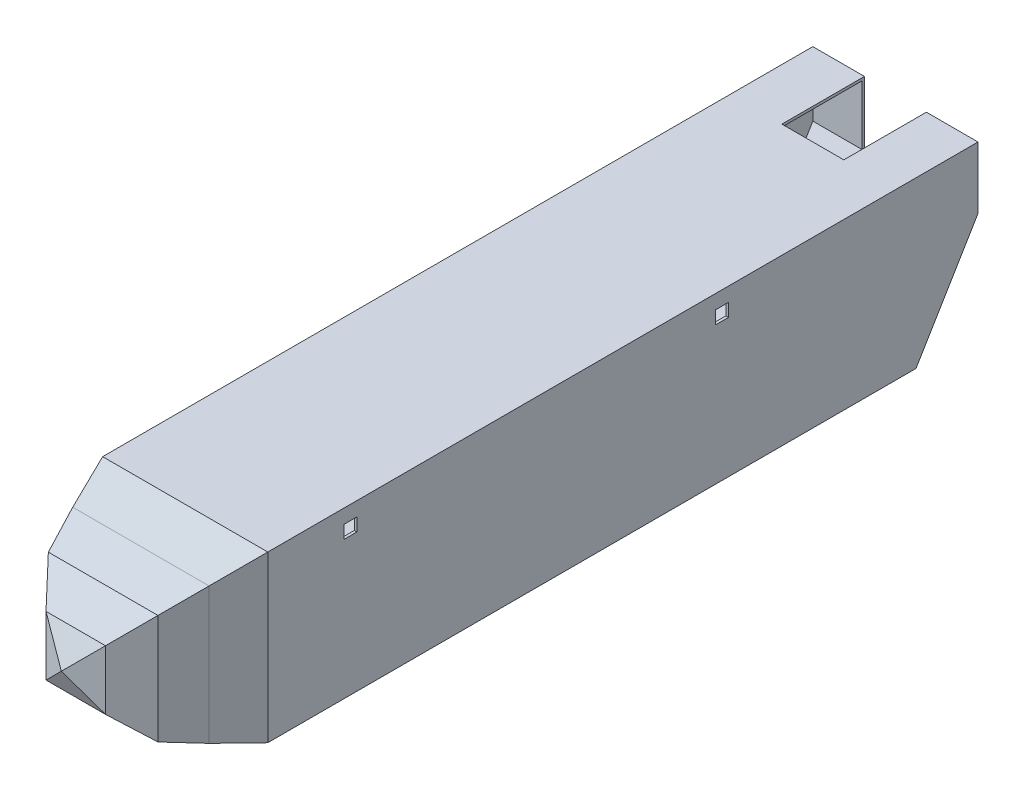
SolidWorks part; units mm, degrees
material "Balsa"
ref_plane "Front Plane" through (0, 0, 0) normal (0, 0, 1) x (1, 0, 0)
ref_plane "Top Plane" through (0, 0, 0) normal (0, 1, 0) x (1, 0, 0)
ref_plane "Right Plane" through (0, 0, 0) normal (1, 0, 0) x (0, 0, -1)
sketch "Sketch1" plane through (0, 0, 0) normal (0, 0, 1) x (1, 0, 0)
  line L1 (-50.8, -50.8) -> (50.8, -50.8)
  line L2 (-50.8, -50.8) -> (-50.8, 50.8)
  line L3 (-50.8, 50.8) -> (50.8, 50.8)
  line L4 (50.8, -50.8) -> (50.8, 50.8)
  line L5 (-50.8, -50.8) -> (50.8, 50.8) construction
  line L6 (-50.8, 50.8) -> (50.8, -50.8) construction
  point P0 (0, 0)
  dimension "D1" = 101.6
  dimension "D2" = 101.6
extrude "Boss-Extrude1" add sketch "Sketch1" along normal blind 436.88 contours L2 L1 L4 L3
ref_plane "Plane1" through (0, 0, 464.1566) normal (0, 0, 1) x (1, 0, 0)
sketch "Sketch3" plane through (0, 0, 464.1566) normal (0, 0, 1) x (1, 0, 0)
  line L1 (-41.9373, -41.9373) -> (41.9373, -41.9373)
  line L2 (-41.9373, -41.9373) -> (-41.9373, 41.9373)
  line L3 (-41.9373, 41.9373) -> (41.9373, 41.9373)
  line L4 (41.9373, -41.9373) -> (41.9373, 41.9373)
  line L5 (-41.9373, -41.9373) -> (41.9373, 41.9373) construction
  line L6 (-41.9373, 41.9373) -> (41.9373, -41.9373) construction
  point P0 (0, 0)
  dimension "D1" = 83.8746
  dimension "D2" = 83.8746
sketch "Sketch5" plane through (0, 0, 436.88) normal (0, 0, 1) x (1, 0, 0)
  line L0 (50.8, -50.8) -> (50.8, 50.8) construction
  line L1 (-50.8, 50.8) -> (50.8, 50.8) construction
  line L2 (-50.8, -50.8) -> (-50.8, 50.8) construction
  line L3 (-50.8, -50.8) -> (50.8, -50.8) construction
  line L4 (50.8, -50.8) -> (50.8, 50.8)
  line L5 (-50.8, 50.8) -> (50.8, 50.8)
  line L6 (-50.8, -50.8) -> (-50.8, 50.8)
  line L7 (-50.8, -50.8) -> (50.8, -50.8)
  dimension "D1" = 101.6
  dimension "D2" = 101.6
loft "Loft2" add profiles "Sketch5", "Sketch3" connector at (-50.8, 50.8, 436.88) connector at (-41.9373, 41.9373, 464.1566)
ref_plane "Plane2" through (0, 0, 487.3594) normal (0, 0, 1) x (1, 0, 0)
sketch "Sketch6" plane through (0, 0, 487.3594) normal (0, 0, 1) x (1, 0, 0)
  line L1 (-33.716, -33.716) -> (33.716, -33.716)
  line L2 (-33.716, -33.716) -> (-33.716, 33.716)
  line L3 (-33.716, 33.716) -> (33.716, 33.716)
  line L4 (33.716, -33.716) -> (33.716, 33.716)
  line L5 (-33.716, -33.716) -> (33.716, 33.716) construction
  line L6 (-33.716, 33.716) -> (33.716, -33.716) construction
  point P0 (0, 0)
loft "Loft3" add profiles "Sketch3<6>", "Sketch6" connector at (-41.9373, 41.9373, 464.1566) connector at (-33.716, 33.716, 487.3594)
sketch "Sketch3<6>" plane through (0, 0, 464.1566) normal (0, 0, 1) x (1, 0, 0) same geometry as "Sketch3"
ref_plane "Plane3" through (0, 0, 504.2173) normal (0, 0, 1) x (1, 0, 0)
sketch "Sketch7" plane through (0, 0, 504.2173) normal (0, 0, 1) x (1, 0, 0)
  line L5 (-41.9373, -41.9373) -> (41.9373, 41.9373) construction
  line L6 (-18.3041, -18.3041) -> (18.3041, -18.3041)
  line L8 (-18.3041, -18.3041) -> (-18.3041, 18.3041)
  line L9 (-18.3041, 18.3041) -> (18.3041, 18.3041)
  line L10 (18.3041, -18.3041) -> (18.3041, 18.3041)
  line L11 (-18.3041, -18.3041) -> (18.3041, 18.3041) construction
  line L12 (-18.3041, 18.3041) -> (18.3041, -18.3041) construction
  point P1 (0, 0)
loft "Loft4" add profiles "Sketch6<4>", "Sketch7" connector at (33.716, 33.716, 487.3594) connector at (18.3041, 18.3041, 504.2173)
sketch "Sketch6<4>" plane through (0, 0, 487.3594) normal (0, 0, 1) x (1, 0, 0) same geometry as "Sketch6"
sketch3d "3DSketch1" plane through (0, 0, 0) normal (0, 0, 1) x (1, 0, 0)
  dimension "D1" = 8.8627
sketch "Sketch8" plane through (0, 0, 513.08) normal (0, 0, 1) x (1, 0, 0)
  point P0 (0, 0)
loft "Loft5" add profiles "Sketch8", "Sketch7<5>"
sketch "Sketch7<5>" plane through (0, 0, 504.2173) normal (0, 0, 1) x (1, 0, 0) same geometry as "Sketch7"
shell "Shell1" thickness 1.5875 removed face at (0, 0, 0)
sketch "Sketch9" plane through (50.8, 0, 0) normal (1, 0, 0) x (0, 0, -1)
  line L0 (-436.88, 50.8) -> (-436.88, 38.1)
  line L1 (-436.88, -50.8) -> (-436.88, 50.8) construction
  line L2 (-436.88, 38.1) -> (-386.08, 38.1)
  line L3 (-386.08, 38.1) -> (-157.48, 38.1)
  line L5 (-390.0805, 34.0995) -> (-382.0795, 34.0995)
  line L6 (-390.0805, 34.0995) -> (-390.0805, 42.1005)
  line L7 (-390.0805, 42.1005) -> (-382.0795, 42.1005)
  line L8 (-382.0795, 34.0995) -> (-382.0795, 42.1005)
  line L9 (-390.0805, 34.0995) -> (-382.0795, 42.1005) construction
  line L10 (-390.0805, 42.1005) -> (-382.0795, 34.0995) construction
  line L11 (-161.4805, 34.0995) -> (-153.4795, 34.0995)
  line L12 (-161.4805, 34.0995) -> (-161.4805, 42.1005)
  line L13 (-161.4805, 42.1005) -> (-153.4795, 42.1005)
  line L14 (-153.4795, 34.0995) -> (-153.4795, 42.1005)
  line L15 (-161.4805, 34.0995) -> (-153.4795, 42.1005) construction
  line L16 (-161.4805, 42.1005) -> (-153.4795, 34.0995) construction
  dimension "D4" = 8.001
  dimension "D5" = 8.001
  dimension "D1" = 12.7
  dimension "D2" = 50.8
  dimension "D3" = 228.6
  dimension "D6" = 8.001
  dimension "D7" = 8.001
extrude "Cut-Extrude1" cut sketch "Sketch9" against normal through all contours L5 L8 L3 L2 L6 | L3 L8 L7 L6 L2 | L11 L14 L13 L12 region at (50.8, 40.1002, 386.08) region at (50.8, 36.0997, 386.08) region at (50.8, 40.1002, 161.3673)
sketch "Sketch10" plane through (50.8, 0, 0) normal (1, 0, 0) x (0, 0, -1)
  line L0 (-436.88, 50.8) -> (0, 50.8) construction
  line L3 (0, 50.8) -> (-68.9584, 50.8)
  line L4 (-68.9584, -50.8) -> (-68.9584, 50.8)
  line L5 (0, 50.8) -> (0, 12.7)
  line L6 (0, -50.8) -> (-38.1, -50.8)
  line L7 (0, 12.7) -> (-38.1, -50.8)
  line L8 (0, 12.7) -> (0, -50.8)
  line M16 (0, -50.8) -> (0, 50.8)
  line M19 (-436.88, -50.8) -> (0, -50.8)
  dimension "D1" = 38.1
  dimension "D2" = 38.1
  dimension "D3" = 63.5
extrude "Cut-Extrude2" cut sketch "Sketch10" against normal through all contours L7 M16 M19 region at (50.8, -29.6333, 12.7)
sketch "Sketch11" plane through (50.8, 0, 0) normal (1, 0, 0) x (0, 0, -1)
  line L0 (-38.1, -50.8) -> (-39.6875, -50.8)
  line L1 (-436.88, -50.8) -> (-38.1, -50.8) construction
  line L2 (0, 50.8) -> (-1.5875, 50.8)
  line L3 (-436.88, 50.8) -> (0, 50.8) construction
  line L4 (-1.5875, 50.8) -> (-1.5875, 12.7)
  line L5 (0, 50.8) -> (0, 12.7)
  line L6 (-1.5875, 12.7) -> (-39.6875, -50.8)
  line L7 (0, 12.7) -> (-38.1, -50.8)
  dimension "D1" = 1.5875
  dimension "D2" = 1.5875
extrude "Boss-Extrude2" add sketch "Sketch11" against normal blind 101.6
sketch "Sketch12" plane through (0, 0, 0) normal (0, 0, -1) x (-1, 0, 0)
  line L0 (-50.8, 50.8) -> (-19.05, 50.8)
  line L1 (50.8, 50.8) -> (-50.8, 50.8) construction
  line L2 (50.8, 12.7) -> (-50.8, 12.7) construction
  line L3 (-19.05, 50.8) -> (19.05, 50.8)
  line L4 (-19.05, 50.8) -> (-19.05, 12.7)
  line L5 (-19.05, 12.7) -> (19.05, 12.7)
  line L6 (19.05, 50.8) -> (19.05, 12.7)
  line M7 (-50.8, 12.7) -> (50.8, 12.7)
  line M9 (50.8, 50.8) -> (-50.8, 50.8)
  dimension "D1" = 31.75
  dimension "D2" = 38.1
extrude "Cut-Extrude3" cut sketch "Sketch12" against normal blind 50.8 contours L6 L4 M9 M7 region at (0, 31.75, 0)
equation "\"Fuse_Diam\"= 4"
equation "\"D2@Sketch1\"=\"Fuse_Diam\""
equation "\"D1@Sketch1\"=\"Fuse_Diam\""
equation "\"Magic Line\"= 3 / ( cos ( 18 ) + cos ( 2 * 18 ) + cos ( 3 * 18 ) + cos ( 4 * 18 ) )"
equation "\"Second Stage Cone\"= 3.30215"
equation "\"D1@Sketch3\"=\"Second Stage Cone\""
equation "\"D2@Sketch3\"=\"Second Stage Cone\""
